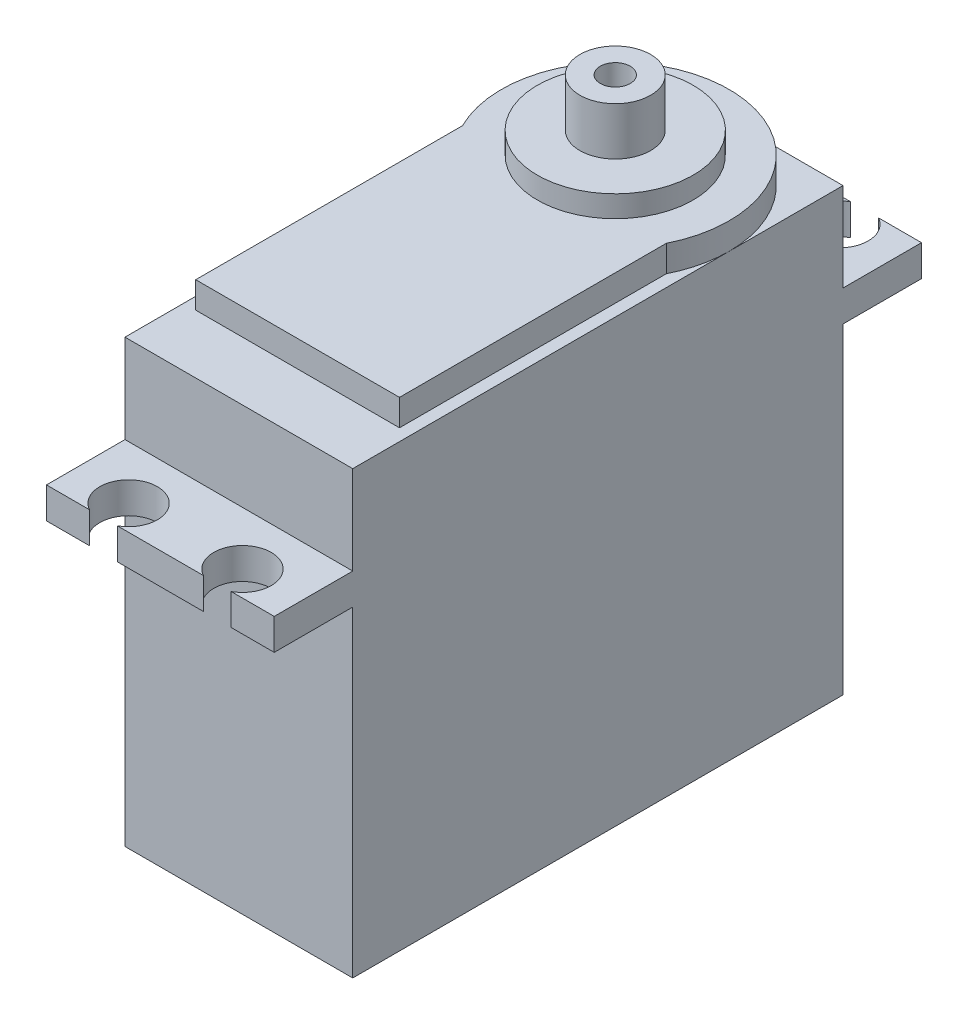
SolidWorks part; units mm, degrees
ref_plane "Front Plane" through (0, 0, 0) normal (0, 0, 1) x (1, 0, 0)
ref_plane "Top Plane" through (0, 0, 0) normal (0, 1, 0) x (1, 0, 0)
ref_plane "Right Plane" through (0, 0, 0) normal (1, 0, 0) x (0, 0, -1)
sketch "Sketch1" plane through (0, 0, 0) normal (1, 0, 0) x (0, 0, -1)
  line L1 (-20.45, 18.4) -> (20.45, 18.4)
  line L2 (-20.45, 18.4) -> (-20.45, -18.4)
  line L3 (-20.45, -18.4) -> (20.45, -18.4)
  line L4 (20.45, 18.4) -> (20.45, -18.4)
  line L5 (-20.45, 18.4) -> (20.45, -18.4) construction
  line L6 (-20.45, -18.4) -> (20.45, 18.4) construction
  point P0 (0, 0)
  dimension "D1" = 36.8
  dimension "D2" = 40.9
extrude "Boss-Extrude1" add sketch "Sketch1" along normal blind 19
sketch "Sketch2" plane through (0, 0, 20.45) normal (0, 0, 1) x (1, 0, 0)
  line L0 (19, 18.4) -> (19, -18.4) construction
  line L1 (0, 8.4) -> (19, 8.4)
  line L2 (0, 8.4) -> (0, -18.4)
  line L3 (0, -18.4) -> (19, -18.4)
  line L4 (19, 8.4) -> (19, -18.4)
  line L5 (0, 8.4) -> (19, -18.4) construction
  line L6 (0, -18.4) -> (19, 8.4) construction
  line L7 (19, -18.4) -> (0, -18.4) construction
  line L8 (0, 18.4) -> (0, -18.4) construction
  line L10 (0, 11) -> (19, 11)
  line L11 (0, 11) -> (0, 8.4)
  line L12 (0, 8.4) -> (19, 8.4)
  line L13 (19, 11) -> (19, 8.4)
  line L14 (0, 11) -> (19, 8.4) construction
  line L15 (0, 8.4) -> (19, 11) construction
  point P0 (9.5, -5)
  point P11 (9.5, 9.7)
  line M4 (0, 18.4) -> (0, -18.4)
  line M6 (19, -18.4) -> (19, 18.4)
  dimension "D1" = 26.8
  dimension "D2" = 2.6
extrude "Boss-Extrude2" add sketch "Sketch2" along normal blind 6.55 from surface contours L10 L1 M4 M6 region at (9.5, 9.7, 20.45) starting at face at (9.5, 0, 20.45)
sketch "Sketch3" plane through (0, 0, -20.45) normal (0, 0, -1) x (-1, 0, 0)
  line L0 (0, -18.4) -> (0, 18.4) construction
  line L1 (-19, 8.4) -> (0, 8.4)
  line L2 (-19, 8.4) -> (-19, -18.4)
  line L3 (-19, -18.4) -> (0, -18.4)
  line L4 (0, 8.4) -> (0, -18.4)
  line L5 (-19, 8.4) -> (0, -18.4) construction
  line L6 (-19, -18.4) -> (0, 8.4) construction
  line L7 (-19, -18.4) -> (0, -18.4) construction
  line L8 (-19, -18.4) -> (-19, 18.4) construction
  line L14 (-19, 11) -> (0, 11)
  line L15 (-19, 11) -> (-19, 8.4)
  line L16 (-19, 8.4) -> (0, 8.4)
  line L17 (0, 11) -> (0, 8.4)
  line L18 (-19, 11) -> (0, 8.4) construction
  line L19 (-19, 8.4) -> (0, 11) construction
  point P0 (-9.5, -5)
  point P11 (-9.5, 9.7)
  line M4 (0, -18.4) -> (0, 18.4)
  line M6 (-19, 18.4) -> (-19, -18.4)
  dimension "D1" = 26.8
  dimension "D2" = 2.6
extrude "Boss-Extrude3" add sketch "Sketch3" along normal blind 6.55 from surface contours L14 L1 M6 M4 region at (9.5, 9.7, -20.45) starting at face at (9.5, 0, -20.45)
sketch "Sketch4" plane through (0, 18.4, 0) normal (0, 1, 0) x (1, 0, 0)
  line L0 (19, 20.45) -> (0, 20.45) construction
  line L1 (19, 20.45) -> (19, -20.45) construction
  line L2 (0, 20.45) -> (0, -20.45) construction
  line L3 (9.5, 20.45) -> (9.5, -20.45) construction
  line L4 (1, 10.95) -> (18, 10.95)
  line L5 (1, 10.95) -> (1, -15.55)
  line L6 (1, -15.55) -> (18, -15.55)
  line L7 (18, 10.95) -> (18, -15.55)
  line L8 (1, 10.95) -> (18, -15.55) construction
  line L9 (1, -15.55) -> (18, 10.95) construction
  line L10 (0, -20.45) -> (19, -20.45) construction
  circle A0 centre (9.5, 10.95) radius 9.5
  circle A1 centre (9.5, 10.95) radius 6.5
  circle A2 centre (9.5, 10.95) radius 2.95
  circle A3 centre (9.5, 10.95) radius 1.25
  point P8 (9.5, -2.3)
  dimension "D1" = 26.5
  dimension "D3" = 13
  dimension "D4" = 5.9
  dimension "D5" = 2.5
  dimension "D2" = 17
extrude "Boss-Extrude4" add sketch "Sketch4" along normal blind 2.2 from surface contours A1 L4 L7 A0 L5 | A1 L4 L5 A0 L7 | A2 L4 A1 | A3 L4 A2 | A3 L4 A2 | L4 A3 | L4 A3 | A2 L4 A1 | A0 L5 L6 L7 region at (9.5, 18.4, -12.3599) region at (9.5, 18.4, -10.4195) region at (9.5, 18.4, -11.4805) region at (9.5, 18.4, -9.5401) region at (9.5, 18.4, -14.0995) region at (9.5, 18.4, -7.8005) region at (9.5, 18.4, -17.6845) region at (17, 18.4, -10.7553) region at (9.5, 18.4, 6.2439) starting at face at (9.5, 18.4, 0)
extrude "Boss-Extrude5" add sketch "Sketch4<4>" along normal blind 1.8 from surface contours A2 L4 A1 | A3 L4 A2 | A3 L4 A2 | A2 L4 A1 | L4 A3 | L4 A3 region at (9.5, 18.4, -12.3599) region at (9.5, 18.4, -10.4195) region at (9.5, 18.4, -11.4805) region at (9.5, 18.4, -9.5401) region at (9.5, 18.4, -14.0995) region at (9.5, 18.4, -7.8005) starting at face at (9.5, 20.6, 0.9857)
sketch "Sketch4<4>" plane through (0, 18.4, 0) normal (0, 1, 0) x (1, 0, 0) same geometry as "Sketch4"
extrude "Boss-Extrude6" add sketch "Sketch4<6>" along normal blind 4 from surface contours A3 L4 A2 | A3 L4 A2 region at (9.5, 18.4, -12.3599) region at (9.5, 18.4, -9.5401) starting at face at (9.5, 22.4, -17.45)
sketch "Sketch4<6>" plane through (0, 18.4, 0) normal (0, 1, 0) x (1, 0, 0) same geometry as "Sketch4"
sketch "Sketch8" plane through (0, 11, 0) normal (0, 1, 0) x (1, 0, 0)
  line L0 (9.5, -24.75) -> (0, -24.75) construction
  line L1 (0, -22.5) -> (19, -22.5)
  line L2 (0, -22.5) -> (0, -27)
  line L3 (0, -27) -> (19, -27)
  line L4 (19, -22.5) -> (19, -27)
  line L5 (0, -22.5) -> (19, -27) construction
  line L6 (0, -27) -> (19, -22.5) construction
  line L7 (19, -27) -> (19, -20.45) construction
  line L8 (0, -27) -> (19, -27) construction
  line L9 (0, -27) -> (0, -20.45) construction
  line L10 (9.5, -27) -> (9.5, 27) construction
  line L11 (19, 27) -> (0, 27) construction
  line L12 (9.5, -24.75) -> (19, -24.75) construction
  line L13 (4.75, -24.75) -> (4.75, -22.5) construction
  line L14 (4.75, -22.5) -> (4.75, -27) construction
  line L15 (14.25, -24.75) -> (14.25, -22.5) construction
  line L16 (14.25, -22.5) -> (14.25, -27) construction
  circle A0 centre (4.75, -24.9) radius 2.4
  circle A1 centre (14.25, -24.9) radius 2.4
  point P0 (9.5, -24.75)
  dimension "D1" = 4.8
  dimension "D2" = 4.8
  dimension "D3" = 4.5
extrude "Cut-Extrude1" cut sketch "Sketch8" against normal blind 2.6 from surface contours L3 A0 | L3 A1 region at (4.75, 11, 24.8407) region at (14.25, 11, 24.8407) starting at face at (9.5, 11, 23.725)
mirror "Mirror1" about plane through (0, 0, 0) normal (0, 0, 1) of "Cut-Extrude1"
